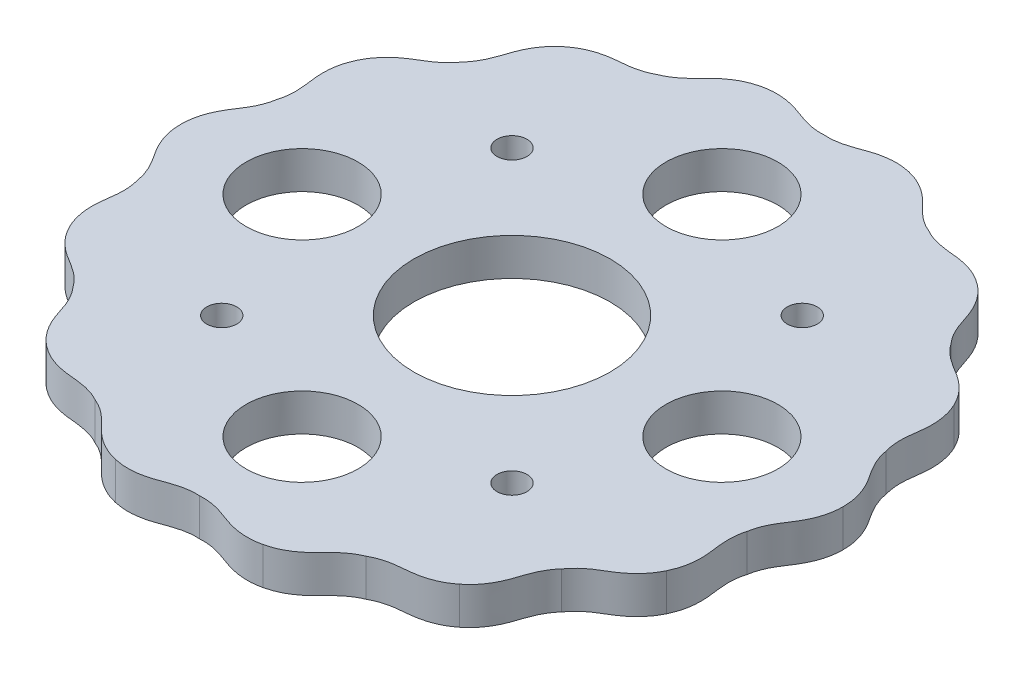
SolidWorks part; units mm, degrees
ref_plane "Front Plane" through (0, 0, 0) normal (0, 0, 1) x (1, 0, 0)
ref_plane "Top Plane" through (0, 0, 0) normal (0, 1, 0) x (1, 0, 0)
ref_plane "Right Plane" through (0, 0, 0) normal (1, 0, 0) x (0, 0, -1)
sketch "Sketch1" plane through (0, 0, 0) normal (0, 1, 0) x (1, 0, 0)
  line L0 (0, 0) -> (37.5, 0) construction
  line L1 (0, 0) -> (37.4807, 1.2019) construction
  line L2 (0, 0) -> (37.423, 2.4026) construction
  line L3 (0, 0) -> (37.3267, 3.6009) construction
  line L4 (0, 0) -> (37.1921, 4.7954) construction
  line L5 (0, 0) -> (37.0193, 5.985) construction
  line L6 (0, 0) -> (36.8085, 7.1684) construction
  line L7 (0, 0) -> (36.5598, 8.3445) construction
  line L8 (0, 0) -> (36.2736, 9.512) construction
  line L9 (0, 0) -> (35.95, 10.6698) construction
  line L10 (0, 0) -> (35.5896, 11.8166) construction
  line L11 (0, 0) -> (35.1926, 12.9512) construction
  line L12 (0, 0) -> (34.7594, 14.0725) construction
  line L13 (0, 0) -> (34.2905, 15.1794) construction
  line L14 (0, 0) -> (33.7863, 16.2706) construction
  line L15 (37.5, 0) -> (38.5, 0) construction
  line L16 (37.4807, 1.2019) -> (38.3521, 1.6927) construction
  line L17 (37.423, 2.4026) -> (37.9413, 3.2578) construction
  line L18 (37.3267, 3.6009) -> (37.3588, 4.6003) construction
  line L19 (37.1921, 4.7954) -> (36.7296, 5.682) construction
  line L20 (37.0193, 5.985) -> (36.1812, 6.5305) construction
  line L21 (36.8085, 7.1684) -> (35.8105, 7.2325) construction
  line L22 (36.5598, 8.3445) -> (35.5849, 8.122) construction
  line L23 (37, 0.0019) -> (37, 0)
  line L24 (33.3367, 16.052) -> (33.3358, 16.0537)
  line L25 (37, -0.0019) -> (37, 0)
  line L26 (33.3367, -16.052) -> (33.3358, -16.0537)
  line L27 (33.335, -16.0554) -> (33.3358, -16.0537)
  line L28 (23.0706, -28.9266) -> (23.0691, -28.9278)
  line L29 (23.0677, -28.9289) -> (23.0691, -28.9278)
  line L30 (8.2351, -36.0719) -> (8.2333, -36.0723)
  line L31 (8.2315, -36.0727) -> (8.2333, -36.0723)
  line L32 (-8.2315, -36.0727) -> (-8.2333, -36.0723)
  line L33 (-8.2351, -36.0719) -> (-8.2333, -36.0723)
  line L34 (-23.0677, -28.9289) -> (-23.0691, -28.9278)
  line L35 (-23.0706, -28.9266) -> (-23.0691, -28.9278)
  line L36 (-33.335, -16.0554) -> (-33.3358, -16.0537)
  line L37 (-33.3367, -16.052) -> (-33.3358, -16.0537)
  line L38 (-37, -0.0019) -> (-37, 0)
  line L39 (-37, 0.0019) -> (-37, 0)
  line L40 (-33.3367, 16.052) -> (-33.3358, 16.0537)
  line L41 (-33.335, 16.0554) -> (-33.3358, 16.0537)
  line L42 (-23.0706, 28.9266) -> (-23.0691, 28.9278)
  line L43 (-23.0677, 28.9289) -> (-23.0691, 28.9278)
  line L44 (-8.2351, 36.0719) -> (-8.2333, 36.0723)
  line L45 (-8.2315, 36.0727) -> (-8.2333, 36.0723)
  line L46 (8.2315, 36.0727) -> (8.2333, 36.0723)
  line L47 (8.2351, 36.0719) -> (8.2333, 36.0723)
  line L48 (23.0677, 28.9289) -> (23.0691, 28.9278)
  line L49 (23.0706, 28.9266) -> (23.0691, 28.9278)
  line L50 (33.335, 16.0554) -> (33.3358, 16.0537)
  line L51 (35.5, 0.0037) -> (35.5, 0)
  line L52 (31.986, 15.3995) -> (31.9844, 15.4029)
  line L53 (35.5, -0.0037) -> (35.5, 0)
  line L54 (31.986, -15.3995) -> (31.9844, -15.4029)
  line L55 (31.9828, -15.4062) -> (31.9844, -15.4029)
  line L56 (22.1368, -27.7527) -> (22.1339, -27.755)
  line L57 (22.131, -27.7573) -> (22.1339, -27.755)
  line L58 (7.9031, -34.6091) -> (7.8995, -34.6099)
  line L59 (7.8959, -34.6108) -> (7.8995, -34.6099)
  line L60 (-7.8959, -34.6108) -> (-7.8995, -34.6099)
  line L61 (-7.9031, -34.6091) -> (-7.8995, -34.6099)
  line L62 (-22.131, -27.7573) -> (-22.1339, -27.755)
  line L63 (-22.1368, -27.7527) -> (-22.1339, -27.755)
  line L64 (-31.9828, -15.4062) -> (-31.9844, -15.4029)
  line L65 (-31.986, -15.3995) -> (-31.9844, -15.4029)
  line L66 (-35.5, -0.0037) -> (-35.5, 0)
  line L67 (-35.5, 0.0037) -> (-35.5, 0)
  line L68 (-31.986, 15.3995) -> (-31.9844, 15.4029)
  line L69 (-31.9828, 15.4062) -> (-31.9844, 15.4029)
  line L70 (-22.1368, 27.7527) -> (-22.1339, 27.755)
  line L71 (-22.131, 27.7573) -> (-22.1339, 27.755)
  line L72 (-7.9031, 34.6091) -> (-7.8995, 34.6099)
  line L73 (-7.8959, 34.6108) -> (-7.8995, 34.6099)
  line L74 (7.8959, 34.6108) -> (7.8995, 34.6099)
  line L75 (7.9031, 34.6091) -> (7.8995, 34.6099)
  line L76 (22.131, 27.7573) -> (22.1339, 27.755)
  line L77 (22.1368, 27.7527) -> (22.1339, 27.755)
  line L78 (31.9828, 15.4062) -> (31.9844, 15.4029)
  circle A0 centre (0, 0) radius 35 construction
  circle A1 centre (37.5, 0) radius 2.5 construction
  circle A2 centre (0, 0) radius 37.5 construction
  spline S0 degree 3 poles (35.5849, 8.122) (35.6266, 7.5364) (36.0345, 6.7125) (36.7836, 5.6218) (37.4152, 4.5501) (38.2239, 2.702) (38.5014, 1.1074) (38.5, 0) knots 0 0 0 0 0.195516 0.310928 0.453873 0.621058 1 1 1 1
  spline S1 degree 3 poles (35.5849, 8.122) (35.3683, 8.6678) (35.3784, 9.5871) (35.5801, 10.8948) (35.6841, 12.1344) (35.611, 14.1503) (35.169, 15.7074) (34.6873, 16.7045) knots 0 0 0 0 0.195516 0.310928 0.453873 0.621058 1 1 1 1
  spline S2 degree 1 poles (34.1119, 7.7858) (33.3367, 16.052) knots 0 0 1 1 construction
  spline S3 degree 1 poles (34.1119, 7.7858) (37, 0.0019) knots 0 0 1 1 construction
  spline S4 degree 3 poles (33.3367, 16.052) (33.6005, 15.5058) (33.9037, 14.6401) (34.1146, 13.4372) (34.174, 12.5211) (34.1413, 11.5771) (34.0239, 10.6392) (33.8823, 9.6155) (33.9055, 8.625) (34.0243, 8.0514) (34.1119, 7.7858) knots 0.015853 0.015853 0.015853 0.015853 0.26189 0.384908 0.507927 0.630945 0.753963 0.876982 0.938491 1 1 1 1
  spline S5 degree 3 poles (34.1119, 7.7858) (34.1483, 7.5085) (34.2901, 6.9402) (34.6989, 6.0377) (35.2706, 5.1769) (35.7834, 4.3828) (36.2224, 3.5464) (36.5664, 2.6953) (36.8983, 1.52) (37.0008, 0.6085) (37, 0.0019) knots 0.015853 0.015853 0.015853 0.015853 0.077362 0.138872 0.26189 0.384908 0.507927 0.630945 0.753963 1 1 1 1
  spline S6 degree 3 poles (37, -0.0019) (37.0008, -0.6085) (36.8983, -1.52) (36.5664, -2.6953) (36.2224, -3.5464) (35.7834, -4.3828) (35.2706, -5.1769) (34.6989, -6.0377) (34.2901, -6.9402) (34.1483, -7.5085) (34.1119, -7.7858) knots 0.015853 0.015853 0.015853 0.015853 0.26189 0.384908 0.507927 0.630945 0.753963 0.876982 0.938491 1 1 1 1
  spline S7 degree 3 poles (34.1119, -7.7858) (34.0243, -8.0514) (33.9055, -8.625) (33.8823, -9.6155) (34.0239, -10.6392) (34.1413, -11.5771) (34.174, -12.5211) (34.1146, -13.4372) (33.9037, -14.6401) (33.6005, -15.5058) (33.3367, -16.052) knots 0.015853 0.015853 0.015853 0.015853 0.077362 0.138872 0.26189 0.384908 0.507927 0.630945 0.753963 1 1 1 1
  spline S8 degree 3 poles (33.335, -16.0554) (33.0725, -16.6022) (32.5847, -17.3791) (31.7758, -18.2939) (31.0965, -18.9115) (30.3381, -19.4746) (29.5316, -19.9675) (28.6429, -20.4951) (27.8831, -21.1308) (27.5087, -21.5813) (27.3556, -21.8154) knots 0.015853 0.015853 0.015853 0.015853 0.26189 0.384908 0.507927 0.630945 0.753963 0.876982 0.938491 1 1 1 1
  spline S9 degree 3 poles (27.3556, -21.8154) (27.1615, -22.0167) (26.8056, -22.4819) (26.3549, -23.3642) (26.0383, -24.348) (25.7371, -25.2439) (25.357, -26.1087) (24.906, -26.9083) (24.1941, -27.9005) (23.5453, -28.549) (23.0706, -28.9266) knots 0.015853 0.015853 0.015853 0.015853 0.077362 0.138872 0.26189 0.384908 0.507927 0.630945 0.753963 1 1 1 1
  spline S10 degree 3 poles (23.0677, -28.9289) (22.5939, -29.3077) (21.8173, -29.796) (20.6915, -30.2693) (19.8116, -30.531) (18.884, -30.7092) (17.9435, -30.8034) (16.9139, -30.8931) (15.9535, -31.1362) (15.4207, -31.3797) (15.1812, -31.5241) knots 0.015853 0.015853 0.015853 0.015853 0.26189 0.384908 0.507927 0.630945 0.753963 0.876982 0.938491 1 1 1 1
  spline S11 degree 3 poles (15.1812, -31.5241) (14.919, -31.6213) (14.3964, -31.886) (13.6076, -32.4854) (12.8955, -33.2344) (12.2354, -33.9109) (11.5177, -34.5251) (10.7645, -35.0499) (9.6926, -35.6349) (8.8266, -35.9377) (8.2351, -36.0719) knots 0.015853 0.015853 0.015853 0.015853 0.077362 0.138872 0.26189 0.384908 0.507927 0.630945 0.753963 1 1 1 1
  spline S12 degree 3 poles (8.2315, -36.0727) (7.6402, -36.2085) (6.7287, -36.3114) (5.5091, -36.2494) (4.6028, -36.1034) (3.6897, -35.8614) (2.8014, -35.5383) (1.8349, -35.1724) (0.8641, -34.9747) (0.2785, -34.9629) (0, -34.9891) knots 0.015853 0.015853 0.015853 0.015853 0.26189 0.384908 0.507927 0.630945 0.753963 0.876982 0.938491 1 1 1 1
  spline S13 degree 3 poles (0, -34.9891) (-0.2785, -34.9629) (-0.8641, -34.9747) (-1.8349, -35.1724) (-2.8014, -35.5383) (-3.6897, -35.8614) (-4.6028, -36.1034) (-5.5091, -36.2494) (-6.7287, -36.3114) (-7.6402, -36.2085) (-8.2315, -36.0727) knots 0.015853 0.015853 0.015853 0.015853 0.077362 0.138872 0.26189 0.384908 0.507927 0.630945 0.753963 1 1 1 1
  spline S14 degree 3 poles (-8.2351, -36.0719) (-8.8266, -35.9377) (-9.6926, -35.6349) (-10.7645, -35.0499) (-11.5177, -34.5251) (-12.2354, -33.9109) (-12.8955, -33.2344) (-13.6076, -32.4854) (-14.3964, -31.886) (-14.919, -31.6213) (-15.1812, -31.5241) knots 0.015853 0.015853 0.015853 0.015853 0.26189 0.384908 0.507927 0.630945 0.753963 0.876982 0.938491 1 1 1 1
  spline S15 degree 3 poles (-15.1812, -31.5241) (-15.4207, -31.3797) (-15.9535, -31.1362) (-16.9139, -30.8931) (-17.9435, -30.8034) (-18.884, -30.7092) (-19.8116, -30.531) (-20.6915, -30.2693) (-21.8173, -29.796) (-22.5939, -29.3077) (-23.0677, -28.9289) knots 0.015853 0.015853 0.015853 0.015853 0.077362 0.138872 0.26189 0.384908 0.507927 0.630945 0.753963 1 1 1 1
  spline S16 degree 3 poles (-23.0706, -28.9266) (-23.5453, -28.549) (-24.1941, -27.9005) (-24.906, -26.9083) (-25.357, -26.1087) (-25.7371, -25.2439) (-26.0383, -24.348) (-26.3549, -23.3642) (-26.8056, -22.4819) (-27.1615, -22.0167) (-27.3556, -21.8154) knots 0.015853 0.015853 0.015853 0.015853 0.26189 0.384908 0.507927 0.630945 0.753963 0.876982 0.938491 1 1 1 1
  spline S17 degree 3 poles (-27.3556, -21.8154) (-27.5087, -21.5813) (-27.8831, -21.1308) (-28.6429, -20.4951) (-29.5316, -19.9675) (-30.3381, -19.4746) (-31.0965, -18.9115) (-31.7758, -18.2939) (-32.5847, -17.3791) (-33.0725, -16.6022) (-33.335, -16.0554) knots 0.015853 0.015853 0.015853 0.015853 0.077362 0.138872 0.26189 0.384908 0.507927 0.630945 0.753963 1 1 1 1
  spline S18 degree 3 poles (-33.3367, -16.052) (-33.6005, -15.5058) (-33.9037, -14.6401) (-34.1146, -13.4372) (-34.174, -12.5211) (-34.1413, -11.5771) (-34.0239, -10.6392) (-33.8823, -9.6155) (-33.9055, -8.625) (-34.0243, -8.0514) (-34.1119, -7.7858) knots 0.015853 0.015853 0.015853 0.015853 0.26189 0.384908 0.507927 0.630945 0.753963 0.876982 0.938491 1 1 1 1
  spline S19 degree 3 poles (-34.1119, -7.7858) (-34.1483, -7.5085) (-34.2901, -6.9402) (-34.6989, -6.0377) (-35.2706, -5.1769) (-35.7834, -4.3828) (-36.2224, -3.5464) (-36.5664, -2.6953) (-36.8983, -1.52) (-37.0008, -0.6085) (-37, -0.0019) knots 0.015853 0.015853 0.015853 0.015853 0.077362 0.138872 0.26189 0.384908 0.507927 0.630945 0.753963 1 1 1 1
  spline S20 degree 3 poles (-37, 0.0019) (-37.0008, 0.6085) (-36.8983, 1.52) (-36.5664, 2.6953) (-36.2224, 3.5464) (-35.7834, 4.3828) (-35.2706, 5.1769) (-34.6989, 6.0377) (-34.2901, 6.9402) (-34.1483, 7.5085) (-34.1119, 7.7858) knots 0.015853 0.015853 0.015853 0.015853 0.26189 0.384908 0.507927 0.630945 0.753963 0.876982 0.938491 1 1 1 1
  spline S21 degree 3 poles (-34.1119, 7.7858) (-34.0243, 8.0514) (-33.9055, 8.625) (-33.8823, 9.6155) (-34.0239, 10.6392) (-34.1413, 11.5771) (-34.174, 12.5211) (-34.1146, 13.4372) (-33.9037, 14.6401) (-33.6005, 15.5058) (-33.3367, 16.052) knots 0.015853 0.015853 0.015853 0.015853 0.077362 0.138872 0.26189 0.384908 0.507927 0.630945 0.753963 1 1 1 1
  spline S22 degree 3 poles (-33.335, 16.0554) (-33.0725, 16.6022) (-32.5847, 17.3791) (-31.7758, 18.2939) (-31.0965, 18.9115) (-30.3381, 19.4746) (-29.5316, 19.9675) (-28.6429, 20.4951) (-27.8831, 21.1308) (-27.5087, 21.5813) (-27.3556, 21.8154) knots 0.015853 0.015853 0.015853 0.015853 0.26189 0.384908 0.507927 0.630945 0.753963 0.876982 0.938491 1 1 1 1
  spline S23 degree 3 poles (-27.3556, 21.8154) (-27.1615, 22.0167) (-26.8056, 22.4819) (-26.3549, 23.3642) (-26.0383, 24.348) (-25.7371, 25.2439) (-25.357, 26.1087) (-24.906, 26.9083) (-24.1941, 27.9005) (-23.5453, 28.549) (-23.0706, 28.9266) knots 0.015853 0.015853 0.015853 0.015853 0.077362 0.138872 0.26189 0.384908 0.507927 0.630945 0.753963 1 1 1 1
  spline S24 degree 3 poles (-23.0677, 28.9289) (-22.5939, 29.3077) (-21.8173, 29.796) (-20.6915, 30.2693) (-19.8116, 30.531) (-18.884, 30.7092) (-17.9435, 30.8034) (-16.9139, 30.8931) (-15.9535, 31.1362) (-15.4207, 31.3797) (-15.1812, 31.5241) knots 0.015853 0.015853 0.015853 0.015853 0.26189 0.384908 0.507927 0.630945 0.753963 0.876982 0.938491 1 1 1 1
  spline S25 degree 3 poles (-15.1812, 31.5241) (-14.919, 31.6213) (-14.3964, 31.886) (-13.6076, 32.4854) (-12.8955, 33.2344) (-12.2354, 33.9109) (-11.5177, 34.5251) (-10.7645, 35.0499) (-9.6926, 35.6349) (-8.8266, 35.9377) (-8.2351, 36.0719) knots 0.015853 0.015853 0.015853 0.015853 0.077362 0.138872 0.26189 0.384908 0.507927 0.630945 0.753963 1 1 1 1
  spline S26 degree 3 poles (-8.2315, 36.0727) (-7.6402, 36.2085) (-6.7287, 36.3114) (-5.5091, 36.2494) (-4.6028, 36.1034) (-3.6897, 35.8614) (-2.8014, 35.5383) (-1.8349, 35.1724) (-0.8641, 34.9747) (-0.2785, 34.9629) (0, 34.9891) knots 0.015853 0.015853 0.015853 0.015853 0.26189 0.384908 0.507927 0.630945 0.753963 0.876982 0.938491 1 1 1 1
  spline S27 degree 3 poles (0, 34.9891) (0.2785, 34.9629) (0.8641, 34.9747) (1.8349, 35.1724) (2.8014, 35.5383) (3.6897, 35.8614) (4.6028, 36.1034) (5.5091, 36.2494) (6.7287, 36.3114) (7.6402, 36.2085) (8.2315, 36.0727) knots 0.015853 0.015853 0.015853 0.015853 0.077362 0.138872 0.26189 0.384908 0.507927 0.630945 0.753963 1 1 1 1
  spline S28 degree 3 poles (8.2351, 36.0719) (8.8266, 35.9377) (9.6926, 35.6349) (10.7645, 35.0499) (11.5177, 34.5251) (12.2354, 33.9109) (12.8955, 33.2344) (13.6076, 32.4854) (14.3964, 31.886) (14.919, 31.6213) (15.1812, 31.5241) knots 0.015853 0.015853 0.015853 0.015853 0.26189 0.384908 0.507927 0.630945 0.753963 0.876982 0.938491 1 1 1 1
  spline S29 degree 3 poles (15.1812, 31.5241) (15.4207, 31.3797) (15.9535, 31.1362) (16.9139, 30.8931) (17.9435, 30.8034) (18.884, 30.7092) (19.8116, 30.531) (20.6915, 30.2693) (21.8173, 29.796) (22.5939, 29.3077) (23.0677, 28.9289) knots 0.015853 0.015853 0.015853 0.015853 0.077362 0.138872 0.26189 0.384908 0.507927 0.630945 0.753963 1 1 1 1
  spline S30 degree 3 poles (23.0706, 28.9266) (23.5453, 28.549) (24.1941, 27.9005) (24.906, 26.9083) (25.357, 26.1087) (25.7371, 25.2439) (26.0383, 24.348) (26.3549, 23.3642) (26.8056, 22.4819) (27.1615, 22.0167) (27.3556, 21.8154) knots 0.015853 0.015853 0.015853 0.015853 0.26189 0.384908 0.507927 0.630945 0.753963 0.876982 0.938491 1 1 1 1
  spline S31 degree 3 poles (27.3556, 21.8154) (27.5087, 21.5813) (27.8831, 21.1308) (28.6429, 20.4951) (29.5316, 19.9675) (30.3381, 19.4746) (31.0965, 18.9115) (31.7758, 18.2939) (32.5847, 17.3791) (33.0725, 16.6022) (33.335, 16.0554) knots 0.015853 0.015853 0.015853 0.015853 0.077362 0.138872 0.26189 0.384908 0.507927 0.630945 0.753963 1 1 1 1
  spline S32 degree 1 poles (32.6448, 7.451) (35.5, 0.0037) knots 0 0 1 1 construction
  spline S33 degree 1 poles (32.6448, 7.451) (31.986, 15.3995) knots 0 0 1 1 construction
  spline S34 degree 3 poles (35.5, 0.0037) (35.5006, 0.4959) (35.4183, 1.2336) (35.1496, 2.1927) (34.8707, 2.8896) (34.4997, 3.6015) (34.1394, 4.1652) (33.6939, 4.8394) (33.3068, 5.4873) (32.9751, 6.1975) (32.758, 6.8733) (32.6748, 7.2607) (32.6448, 7.451) knots 0.023011 0.023011 0.023011 0.023011 0.267258 0.389382 0.511505 0.633629 0.755753 0.816814 0.877876 0.938938 0.969469 1 1 1 1
  spline S35 degree 3 poles (32.6448, 7.451) (32.5893, 7.6354) (32.4961, 8.0206) (32.3985, 8.7236) (32.3893, 9.5074) (32.4569, 10.2591) (32.5657, 11.0598) (32.6458, 11.724) (32.6712, 12.5264) (32.6201, 13.2752) (32.446, 14.256) (32.2001, 14.9563) (31.986, 15.3995) knots 0.023011 0.023011 0.023011 0.023011 0.053542 0.084072 0.145134 0.206196 0.267258 0.389382 0.511505 0.633629 0.755753 1 1 1 1
  spline S36 degree 3 poles (32.6448, -7.451) (32.6748, -7.2607) (32.758, -6.8733) (32.9751, -6.1975) (33.3068, -5.4873) (33.6939, -4.8394) (34.1394, -4.1652) (34.4997, -3.6015) (34.8707, -2.8896) (35.1496, -2.1927) (35.4183, -1.2336) (35.5006, -0.4959) (35.5, -0.0037) knots 0.023011 0.023011 0.023011 0.023011 0.053542 0.084072 0.145134 0.206196 0.267258 0.389382 0.511505 0.633629 0.755753 1 1 1 1
  spline S37 degree 3 poles (31.986, -15.3995) (32.2001, -14.9563) (32.446, -14.256) (32.6201, -13.2752) (32.6712, -12.5264) (32.6458, -11.724) (32.5657, -11.0598) (32.4569, -10.2591) (32.3893, -9.5074) (32.3985, -8.7236) (32.4961, -8.0206) (32.5893, -7.6354) (32.6448, -7.451) knots 0.023011 0.023011 0.023011 0.023011 0.267258 0.389382 0.511505 0.633629 0.755753 0.816814 0.877876 0.938938 0.969469 1 1 1 1
  spline S38 degree 3 poles (26.1791, -20.8771) (26.2887, -20.7187) (26.5317, -20.4057) (27.0205, -19.8911) (27.6275, -19.3952) (28.2574, -18.9793) (28.9513, -18.5652) (29.5206, -18.2137) (30.1637, -17.7333) (30.7173, -17.2264) (31.3755, -16.4789) (31.7698, -15.8499) (31.9828, -15.4062) knots 0.023011 0.023011 0.023011 0.023011 0.053542 0.084072 0.145134 0.206196 0.267258 0.389382 0.511505 0.633629 0.755753 1 1 1 1
  spline S39 degree 3 poles (22.1368, -27.7527) (22.522, -27.4463) (23.0474, -26.922) (23.6297, -26.1139) (24.0007, -25.4614) (24.326, -24.7275) (24.542, -24.0943) (24.7914, -23.3257) (25.0566, -22.619) (25.405, -21.9169) (25.798, -21.3258) (26.0491, -21.0192) (26.1791, -20.8771) knots 0.023011 0.023011 0.023011 0.023011 0.267258 0.389382 0.511505 0.633629 0.755753 0.816814 0.877876 0.938938 0.969469 1 1 1 1
  spline S40 degree 3 poles (14.5283, -30.1683) (14.6957, -30.0732) (15.0505, -29.8966) (15.7143, -29.645) (16.4763, -29.4616) (17.2242, -29.3602) (18.0291, -29.2882) (18.6945, -29.2185) (19.4823, -29.0647) (20.201, -28.8482) (21.1184, -28.4603) (21.7465, -28.0647) (22.131, -27.7573) knots 0.023011 0.023011 0.023011 0.023011 0.053542 0.084072 0.145134 0.206196 0.267258 0.389382 0.511505 0.633629 0.755753 1 1 1 1
  spline S41 degree 3 poles (7.9031, -34.6091) (8.3831, -34.5002) (9.084, -34.2557) (9.9593, -33.7804) (10.5766, -33.3534) (11.1881, -32.8334) (11.6575, -32.3566) (12.2156, -31.7723) (12.7612, -31.2507) (13.3797, -30.7693) (13.9903, -30.4072) (14.3495, -30.2399) (14.5283, -30.1683) knots 0.023011 0.023011 0.023011 0.023011 0.267258 0.389382 0.511505 0.633629 0.755753 0.816814 0.877876 0.938938 0.969469 1 1 1 1
  spline S42 degree 3 poles (0, -33.4843) (0.1922, -33.4712) (0.5884, -33.4661) (1.2956, -33.5274) (2.0617, -33.6928) (2.7796, -33.926) (3.536, -34.2103) (4.1657, -34.4362) (4.9423, -34.6394) (5.6838, -34.7562) (6.6786, -34.8048) (7.4161, -34.7209) (7.8959, -34.6108) knots 0.023011 0.023011 0.023011 0.023011 0.053542 0.084072 0.145134 0.206196 0.267258 0.389382 0.511505 0.633629 0.755753 1 1 1 1
  spline S43 degree 3 poles (-7.8959, -34.6108) (-7.4161, -34.7209) (-6.6786, -34.8048) (-5.6838, -34.7562) (-4.9423, -34.6394) (-4.1657, -34.4362) (-3.536, -34.2103) (-2.7796, -33.926) (-2.0617, -33.6928) (-1.2956, -33.5274) (-0.5884, -33.4661) (-0.1922, -33.4712) (0, -33.4843) knots 0.023011 0.023011 0.023011 0.023011 0.267258 0.389382 0.511505 0.633629 0.755753 0.816814 0.877876 0.938938 0.969469 1 1 1 1
  spline S44 degree 3 poles (-14.5283, -30.1683) (-14.3495, -30.2399) (-13.9903, -30.4072) (-13.3797, -30.7693) (-12.7612, -31.2507) (-12.2156, -31.7723) (-11.6575, -32.3566) (-11.1881, -32.8334) (-10.5766, -33.3534) (-9.9593, -33.7804) (-9.084, -34.2557) (-8.3831, -34.5002) (-7.9031, -34.6091) knots 0.023011 0.023011 0.023011 0.023011 0.053542 0.084072 0.145134 0.206196 0.267258 0.389382 0.511505 0.633629 0.755753 1 1 1 1
  spline S45 degree 3 poles (-22.131, -27.7573) (-21.7465, -28.0647) (-21.1184, -28.4603) (-20.201, -28.8482) (-19.4823, -29.0647) (-18.6945, -29.2185) (-18.0291, -29.2882) (-17.2242, -29.3602) (-16.4763, -29.4616) (-15.7143, -29.645) (-15.0505, -29.8966) (-14.6957, -30.0732) (-14.5283, -30.1683) knots 0.023011 0.023011 0.023011 0.023011 0.267258 0.389382 0.511505 0.633629 0.755753 0.816814 0.877876 0.938938 0.969469 1 1 1 1
  spline S46 degree 3 poles (-26.1791, -20.8771) (-26.0491, -21.0192) (-25.798, -21.3258) (-25.405, -21.9169) (-25.0566, -22.619) (-24.7914, -23.3257) (-24.542, -24.0943) (-24.326, -24.7275) (-24.0007, -25.4614) (-23.6297, -26.1139) (-23.0474, -26.922) (-22.522, -27.4463) (-22.1368, -27.7527) knots 0.023011 0.023011 0.023011 0.023011 0.053542 0.084072 0.145134 0.206196 0.267258 0.389382 0.511505 0.633629 0.755753 1 1 1 1
  spline S47 degree 3 poles (-31.9828, -15.4062) (-31.7698, -15.8499) (-31.3755, -16.4789) (-30.7173, -17.2264) (-30.1637, -17.7333) (-29.5206, -18.2137) (-28.9513, -18.5652) (-28.2574, -18.9793) (-27.6275, -19.3952) (-27.0205, -19.8911) (-26.5317, -20.4057) (-26.2887, -20.7187) (-26.1791, -20.8771) knots 0.023011 0.023011 0.023011 0.023011 0.267258 0.389382 0.511505 0.633629 0.755753 0.816814 0.877876 0.938938 0.969469 1 1 1 1
  spline S48 degree 3 poles (-32.6448, -7.451) (-32.5893, -7.6354) (-32.4961, -8.0206) (-32.3985, -8.7236) (-32.3893, -9.5074) (-32.4569, -10.2591) (-32.5657, -11.0598) (-32.6458, -11.724) (-32.6712, -12.5264) (-32.6201, -13.2752) (-32.446, -14.256) (-32.2001, -14.9563) (-31.986, -15.3995) knots 0.023011 0.023011 0.023011 0.023011 0.053542 0.084072 0.145134 0.206196 0.267258 0.389382 0.511505 0.633629 0.755753 1 1 1 1
  spline S49 degree 3 poles (-35.5, -0.0037) (-35.5006, -0.4959) (-35.4183, -1.2336) (-35.1496, -2.1927) (-34.8707, -2.8896) (-34.4997, -3.6015) (-34.1394, -4.1652) (-33.6939, -4.8394) (-33.3068, -5.4873) (-32.9751, -6.1975) (-32.758, -6.8733) (-32.6748, -7.2607) (-32.6448, -7.451) knots 0.023011 0.023011 0.023011 0.023011 0.267258 0.389382 0.511505 0.633629 0.755753 0.816814 0.877876 0.938938 0.969469 1 1 1 1
  spline S50 degree 3 poles (-32.6448, 7.451) (-32.6748, 7.2607) (-32.758, 6.8733) (-32.9751, 6.1975) (-33.3068, 5.4873) (-33.6939, 4.8394) (-34.1394, 4.1652) (-34.4997, 3.6015) (-34.8707, 2.8896) (-35.1496, 2.1927) (-35.4183, 1.2336) (-35.5006, 0.4959) (-35.5, 0.0037) knots 0.023011 0.023011 0.023011 0.023011 0.053542 0.084072 0.145134 0.206196 0.267258 0.389382 0.511505 0.633629 0.755753 1 1 1 1
  spline S51 degree 3 poles (-31.986, 15.3995) (-32.2001, 14.9563) (-32.446, 14.256) (-32.6201, 13.2752) (-32.6712, 12.5264) (-32.6458, 11.724) (-32.5657, 11.0598) (-32.4569, 10.2591) (-32.3893, 9.5074) (-32.3985, 8.7236) (-32.4961, 8.0206) (-32.5893, 7.6354) (-32.6448, 7.451) knots 0.023011 0.023011 0.023011 0.023011 0.267258 0.389382 0.511505 0.633629 0.755753 0.816814 0.877876 0.938938 0.969469 1 1 1 1
  spline S52 degree 3 poles (-26.1791, 20.8771) (-26.2887, 20.7187) (-26.5317, 20.4057) (-27.0205, 19.8911) (-27.6275, 19.3952) (-28.2574, 18.9793) (-28.9513, 18.5652) (-29.5206, 18.2137) (-30.1637, 17.7333) (-30.7173, 17.2264) (-31.3755, 16.4789) (-31.7698, 15.8499) (-31.9828, 15.4062) knots 0.023011 0.023011 0.023011 0.023011 0.053542 0.084072 0.145134 0.206196 0.267258 0.389382 0.511505 0.633629 0.755753 1 1 1 1
  spline S53 degree 3 poles (-22.1368, 27.7527) (-22.522, 27.4463) (-23.0474, 26.922) (-23.6297, 26.1139) (-24.0007, 25.4614) (-24.326, 24.7275) (-24.542, 24.0943) (-24.7914, 23.3257) (-25.0566, 22.619) (-25.405, 21.9169) (-25.798, 21.3258) (-26.0491, 21.0192) (-26.1791, 20.8771) knots 0.023011 0.023011 0.023011 0.023011 0.267258 0.389382 0.511505 0.633629 0.755753 0.816814 0.877876 0.938938 0.969469 1 1 1 1
  spline S54 degree 3 poles (-14.5283, 30.1683) (-14.6957, 30.0732) (-15.0505, 29.8966) (-15.7143, 29.645) (-16.4763, 29.4616) (-17.2242, 29.3602) (-18.0291, 29.2882) (-18.6945, 29.2185) (-19.4823, 29.0647) (-20.201, 28.8482) (-21.1184, 28.4603) (-21.7465, 28.0647) (-22.131, 27.7573) knots 0.023011 0.023011 0.023011 0.023011 0.053542 0.084072 0.145134 0.206196 0.267258 0.389382 0.511505 0.633629 0.755753 1 1 1 1
  spline S55 degree 3 poles (-7.9031, 34.6091) (-8.3831, 34.5002) (-9.084, 34.2557) (-9.9593, 33.7804) (-10.5766, 33.3534) (-11.1881, 32.8334) (-11.6575, 32.3566) (-12.2156, 31.7723) (-12.7612, 31.2507) (-13.3797, 30.7693) (-13.9903, 30.4072) (-14.3495, 30.2399) (-14.5283, 30.1683) knots 0.023011 0.023011 0.023011 0.023011 0.267258 0.389382 0.511505 0.633629 0.755753 0.816814 0.877876 0.938938 0.969469 1 1 1 1
  spline S56 degree 3 poles (0, 33.4843) (-0.1922, 33.4712) (-0.5884, 33.4661) (-1.2956, 33.5274) (-2.0617, 33.6928) (-2.7796, 33.926) (-3.536, 34.2103) (-4.1657, 34.4362) (-4.9423, 34.6394) (-5.6838, 34.7562) (-6.6786, 34.8048) (-7.4161, 34.7209) (-7.8959, 34.6108) knots 0.023011 0.023011 0.023011 0.023011 0.053542 0.084072 0.145134 0.206196 0.267258 0.389382 0.511505 0.633629 0.755753 1 1 1 1
  spline S57 degree 3 poles (7.8959, 34.6108) (7.4161, 34.7209) (6.6786, 34.8048) (5.6838, 34.7562) (4.9423, 34.6394) (4.1657, 34.4362) (3.536, 34.2103) (2.7796, 33.926) (2.0617, 33.6928) (1.2956, 33.5274) (0.5884, 33.4661) (0.1922, 33.4712) (0, 33.4843) knots 0.023011 0.023011 0.023011 0.023011 0.267258 0.389382 0.511505 0.633629 0.755753 0.816814 0.877876 0.938938 0.969469 1 1 1 1
  spline S58 degree 3 poles (14.5283, 30.1683) (14.3495, 30.2399) (13.9903, 30.4072) (13.3797, 30.7693) (12.7612, 31.2507) (12.2156, 31.7723) (11.6575, 32.3566) (11.1881, 32.8334) (10.5766, 33.3534) (9.9593, 33.7804) (9.084, 34.2557) (8.3831, 34.5002) (7.9031, 34.6091) knots 0.023011 0.023011 0.023011 0.023011 0.053542 0.084072 0.145134 0.206196 0.267258 0.389382 0.511505 0.633629 0.755753 1 1 1 1
  spline S59 degree 3 poles (22.131, 27.7573) (21.7465, 28.0647) (21.1184, 28.4603) (20.201, 28.8482) (19.4823, 29.0647) (18.6945, 29.2185) (18.0291, 29.2882) (17.2242, 29.3602) (16.4763, 29.4616) (15.7143, 29.645) (15.0505, 29.8966) (14.6957, 30.0732) (14.5283, 30.1683) knots 0.023011 0.023011 0.023011 0.023011 0.267258 0.389382 0.511505 0.633629 0.755753 0.816814 0.877876 0.938938 0.969469 1 1 1 1
  spline S60 degree 3 poles (26.1791, 20.8771) (26.0491, 21.0192) (25.798, 21.3258) (25.405, 21.9169) (25.0566, 22.619) (24.7914, 23.3257) (24.542, 24.0943) (24.326, 24.7275) (24.0007, 25.4614) (23.6297, 26.1139) (23.0474, 26.922) (22.522, 27.4463) (22.1368, 27.7527) knots 0.023011 0.023011 0.023011 0.023011 0.053542 0.084072 0.145134 0.206196 0.267258 0.389382 0.511505 0.633629 0.755753 1 1 1 1
  spline S61 degree 3 poles (31.9828, 15.4062) (31.7698, 15.8499) (31.3755, 16.4789) (30.7173, 17.2264) (30.1637, 17.7333) (29.5206, 18.2137) (28.9513, 18.5652) (28.2574, 18.9793) (27.6275, 19.3952) (27.0205, 19.8911) (26.5317, 20.4057) (26.2887, 20.7187) (26.1791, 20.8771) knots 0.023011 0.023011 0.023011 0.023011 0.267258 0.389382 0.511505 0.633629 0.755753 0.816814 0.877876 0.938938 0.969469 1 1 1 1
  point P25 (0, 0)
  point P117 (0, 0)
  point P174 (0, 0)
  dimension "D1" = 70
  dimension "D2" = 5
  dimension "D4" = 25.714
  dimension "D5" = 1
  dimension "D7" = 180
  dimension "D8" = 207.551
  dimension "D6" = 1
  dimension "D9" = 1
  dimension "D10" = 235.102
  dimension "D11" = 1
  dimension "D12" = 1
  dimension "D13" = 1
  dimension "D14" = 1
  dimension "D15" = 1
  dimension "D16" = 262.653
  dimension "D17" = 290.204
  dimension "D18" = 317.755
  dimension "D19" = 345.306
  dimension "D20" = 1.5
  dimension "D22" = 3
  dimension "D3" = 15
  dimension "D21" = 14
  dimension "D23" = 14
extrude "Boss-Extrude3" add sketch "Sketch1" along normal blind 4 contours L51 L53 S36 S37 L54 L55 S38 S39 L56 L57 S40 S41 L58 L59 S42 S43 L60 L61 S44 S45 L62 L63 S46 S47 L64 L65 S48 S49 L66 L67 S50 S51 L68 L69 S52 S53 L70 L71 S54 S55 L72 L73 S56 S57 L74 L75 S58 S59 L76 L77 S60 S61 L78 L52 S35 S34
sketch "Sketch2" plane through (0, 4, 0) normal (0, 1, 0) x (1, 0, 0)
  line L0 (0, 0) -> (22.5, 0) construction
  line L1 (0, 0) -> (15.5563, 15.5563) construction
  circle A0 centre (0, 0) radius 10.5159
  circle A1 centre (22.5, 0) radius 6
  circle A6 centre (15.5563, 15.5563) radius 1.607
  circle A7 centre (0, -22.5) radius 6
  circle A8 centre (15.5563, -15.5563) radius 1.607
  circle A9 centre (-22.5, 0) radius 6
  circle A10 centre (-15.5563, -15.5563) radius 1.607
  circle A11 centre (0, 22.5) radius 6
  circle A12 centre (-15.5563, 15.5563) radius 1.607
  point P16 (0, 0)
  point P21 (0, 0)
  point P24 (0, 0)
  dimension "D3" = 12
  dimension "D1" = 21.0317
  dimension "D6" = 3.214
  dimension "D2" = 22.5
  dimension "D4" = 45
  dimension "D5" = 22
  dimension "D7" = 4
extrude "Cut-Extrude1" cut sketch "Sketch2" against normal blind 5 contours A7 | A0 | A0 | A0 | L0 A0 | A0 L0 | A1 | A9 | A11 region at (0, 4, 0) region at (22.5, 4, 0) region at (0, 4, 22.5) region at (-22.5, 4, 0) region at (0, 4, -22.5)
extrude "Cut-Extrude2" cut sketch "Sketch2<4>" against normal blind 2.4105 contours A12 | A10 | A8 | A6 region at (15.5563, 4, -15.5563) region at (15.5563, 4, 15.5563) region at (-15.5563, 4, 15.5563) region at (-15.5563, 4, -15.5563)
sketch "Sketch2<4>" plane through (0, 4, 0) normal (0, 1, 0) x (1, 0, 0) same geometry as "Sketch2"
equation "\"eccentricity\"= 1mm"
equation "\"Pin Diameter\"= 3mm"
equation "\"D5@Sketch1\" = \"eccentricity\""
equation "\"D6@Sketch1\" = \"eccentricity\""
equation "\"D9@Sketch1\" = \"eccentricity\""
equation "\"D11@Sketch1\" = \"eccentricity\""
equation "\"D12@Sketch1\" = \"eccentricity\""
equation "\"D14@Sketch1\" = \"eccentricity\""
equation "\"D13@Sketch1\" = \"eccentricity\""
equation "\"D15@Sketch1\" = \"eccentricity\""
equation "\"Disc Bearing Diameter\"=21"
equation "\"bearing_21_OD\"= 21mm"
equation "\"bearing_21_ID\"=15mm"
equation "\"pin_cirlce_diameter\"= 75mm"
equation "\"pin_diam\"= 6mm"
equation "\"gear_thickness\"= 4mm"
equation "\"ball_bearing_diam\"= 3.214mm"
equation "\"bearing_21_outer_clearance\"= 0.127mm'change this"
equation "\"bearing_21_inner_clearance\"=0mm'change this"
equation "\"bearing_15_OD\"= 15mm"
equation "\"bearing_15_ID\"=10mm"
equation "\"bearing_15_outer_clearance\"= 0mm'change this"
equation "\"bearing_15_inner_clearance\"= 0mm'change this"
equation "\"thrust_bearing_thickness\"= 5mm'measure this irl and change"
equation "\"D1@Sketch2\"=\"bearing_21_OD\"+0.0317mm"
equation "\"D1@Cut-Extrude2\"=\"ball_bearing_diam\"*0.75"
